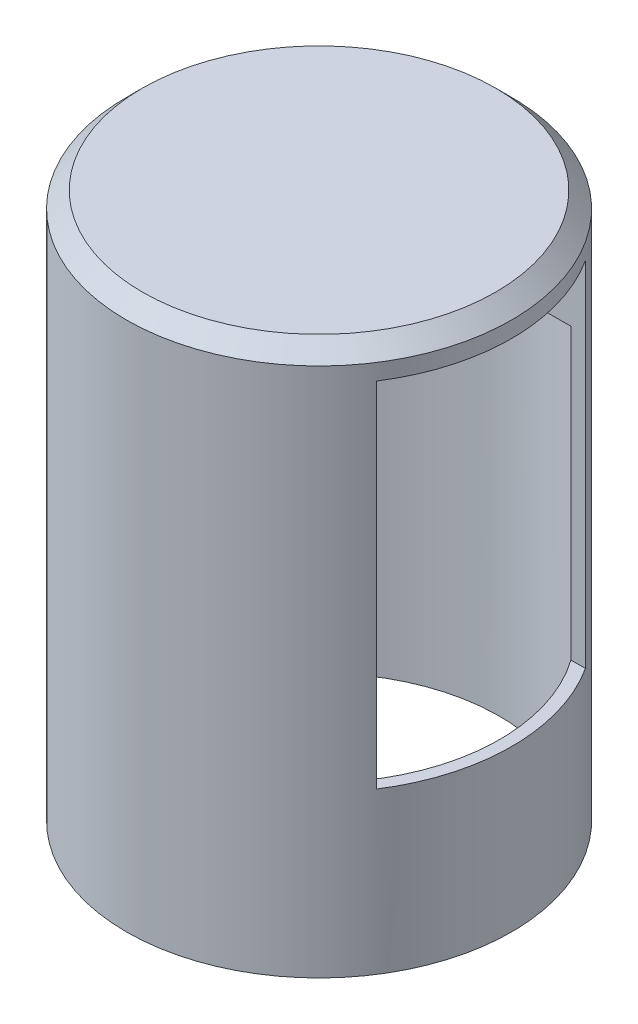
SolidWorks part; units mm, degrees
ref_plane "Front Plane" through (0, 0, 0) normal (0, 0, 1) x (1, 0, 0)
ref_plane "Top Plane" through (0, 0, 0) normal (0, 1, 0) x (1, 0, 0)
ref_plane "Right Plane" through (0, 0, 0) normal (1, 0, 0) x (0, 0, -1)
sketch "Sketch1" plane through (0, 0, 0) normal (0, 1, 0) x (1, 0, 0)
  line L0 (0, 0) -> (0, 22) construction
  line L1 (17.4054, -4.8529) -> (11.8839, -1.665)
  line L2 (12.9054, -12.6471) -> (7.3839, -9.4593)
  line L3 (-4.5, 17.5) -> (-4.5, 11.1243)
  line L4 (4.5, 17.5) -> (4.5, 11.1243)
  line L5 (-12.9054, -12.6471) -> (-7.3839, -9.4593)
  line L6 (-17.4054, -4.8529) -> (-11.8839, -1.665)
  line L7 (0, 0) -> (0, 6.0957) construction
  line L8 (0, 6.5) -> (0, -6.5)
  line L9 (0, 6.5) -> (16.9483, 6.5)
  line L10 (16.9483, 6.5) -> (16.9483, -6.5)
  line L11 (16.9483, -6.5) -> (0, -6.5)
  line L12 (-6.1541, -4.5) -> (-6.1541, -6.5)
  line L13 (0, -6.5) -> (-9.1822, -6.5)
  line L14 (-10.3108, 4.5) -> (10.3108, 4.5) construction
  line L15 (10.3108, -4.5) -> (-10.3108, -4.5) construction
  line L16 (-6.1541, 6.5) -> (-6.1541, 4.5)
  line L17 (-6.1541, 4.5) -> (-4.1541, 4.5)
  line L18 (-4.1541, 4.5) -> (-4.1541, 6.5)
  line L19 (-4.1541, 6.5) -> (-6.1541, 6.5)
  line L20 (-4.1541, -4.5) -> (-4.1541, -6.5)
  line L21 (0, 6.5) -> (-9.1822, 6.5)
  line L22 (-4.1541, -4.5) -> (-6.1541, -4.5)
  line L23 (7.0033, 6.5) -> (7.0033, 4.5)
  line L24 (7.0033, 4.5) -> (5.0033, 4.5)
  line L25 (5.0033, 4.5) -> (5.0033, 6.5)
  line L26 (5.0033, -4.5) -> (5.0033, -6.5)
  line L27 (5.0033, -6.5) -> (5.0033, -4.5)
  line L28 (7.0033, -4.5) -> (7.0033, -6.5)
  line L29 (7.0033, -6.5) -> (7.0033, -4.5)
  line L30 (5.0033, -4.5) -> (7.0033, -4.5)
  circle A0 centre (0, 0) radius 22
  circle A1 centre (0, 0) radius 11.25
  circle A2 centre (0, 0) radius 4
  circle A3 centre (0, 0) radius 17.5 construction
  arc A4 (12.9054, -12.6471) -> (17.4054, -4.8529) centre (15.1554, -8.75) ccw
  circle A5 centre (15.1554, -8.75) radius 2.75
  circle A6 centre (0, 17.5) radius 2.75 construction
  arc A7 (-17.4054, -4.8529) -> (-12.9054, -12.6471) centre (-15.1554, -8.75) ccw
  circle A8 centre (-15.1554, -8.75) radius 2.75
  arc A9 (4.5, 17.5) -> (-4.5, 17.5) centre (0, 17.5) ccw
  circle A10 centre (0, 0) radius 12
  circle A12 centre (0, 17.5) radius 2.75
  point P8 (0, 0)
  point P9 (0, 17.5)
  point P29 (0.0281, 0.078)
  point P32 (0, 0)
  dimension "D1" = 3
  dimension "D2" = 2
  dimension "D4" = 2
extrude "Boss-Extrude1" add sketch "Sketch1" along normal blind 33 contours A10 L11 A1 L9 region at (8.6191, 0, 7.8733)
extrude "Boss-Extrude2" add sketch "Sketch1<6>" along normal blind 1 from offset 32 separate body contours L11 A10 L9 A1 region at (11.1237, 0, 4.1339)
sketch "Sketch1<6>" plane through (0, 0, 0) normal (0, 1, 0) x (1, 0, 0) same geometry as "Sketch1"
extrude "Boss-Extrude3" add sketch "Sketch1<7>" along normal blind 1 from offset 33 contours A10
sketch "Sketch1<7>" plane through (0, 0, 0) normal (0, 1, 0) x (1, 0, 0) same geometry as "Sketch1"
chamfer "Chamfer1" distance 1 angle 45 1 edges at (0, 34, 12)
extrude "Boss-Extrude4" add sketch "Sketch1<8>" along normal blind 10 from offset 0 contours L11 A10 L9 A1 region at (11.1237, 0, 4.1339)
sketch "Sketch1<8>" plane through (0, 0, 0) normal (0, 1, 0) x (1, 0, 0) same geometry as "Sketch1"
extrude "Boss-Extrude5" add sketch "Sketch1<9>" along normal blind 4 from offset 29 contours L20 L22 L12 L13 | L30 L26 L11 L28 | L25 L24 L23 L9 | L18 L19 L16 L17 region at (6.0033, 0, 5.5) region at (6.0033, 0, -5.5) region at (-5.1541, 0, 5.5) region at (-5.1541, 0, -5.5)
sketch "Sketch1<9>" plane through (0, 0, 0) normal (0, 1, 0) x (1, 0, 0) same geometry as "Sketch1"
extrude "Boss-Extrude6" add sketch "Sketch1<11>" along normal blind 5 from offset 28 contours L13 A1 L11 | L9 A1 L21 L19 region at (0, 0, 8.4392) region at (0, 0, -8.4392)
sketch "Sketch1<11>" plane through (0, 0, 0) normal (0, 1, 0) x (1, 0, 0) same geometry as "Sketch1"
